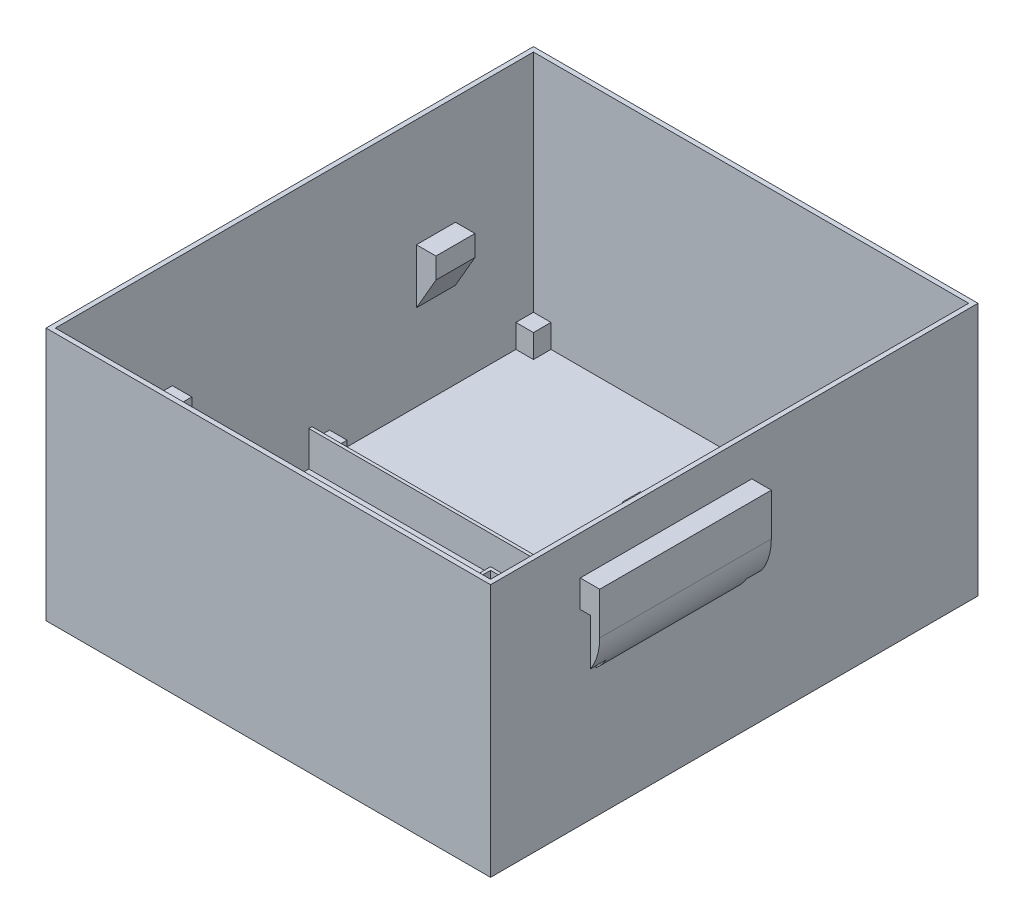
SolidWorks part; units mm, degrees
ref_plane "Front Plane" through (0, 0, 0) normal (0, 0, 1) x (1, 0, 0)
ref_plane "Top Plane" through (0, 0, 0) normal (0, 1, 0) x (1, 0, 0)
ref_plane "Right Plane" through (0, 0, 0) normal (1, 0, 0) x (0, 0, -1)
sketch "Sketch1" plane through (0, 0, 0) normal (0, 1, 0) x (1, 0, 0)
  line L1 (-57, 62.5) -> (57, 62.5)
  line L2 (-57, 62.5) -> (-57, -62.5)
  line L3 (-57, -62.5) -> (57, -62.5)
  line L4 (57, 62.5) -> (57, -62.5)
  line L5 (-57, 62.5) -> (57, -62.5) construction
  line L6 (-57, -62.5) -> (57, 62.5) construction
  point P0 (0, 0)
  dimension "D1" = 125
  dimension "D2" = 114
extrude "Boss-Extrude1" add sketch "Sketch1" along normal blind 65
sketch "Sketch2" plane through (0, 65, 0) normal (0, 1, 0) x (1, 0, 0)
  line L0 (57, -62.5) -> (57, 62.5) construction
  line L1 (-55.8, 61.3) -> (55.8, 61.3)
  line L2 (-55.8, 61.3) -> (-55.8, -61.3)
  line L3 (-55.8, -61.3) -> (55.8, -61.3)
  line L4 (55.8, 61.3) -> (55.8, -61.3)
  line L5 (-55.8, 61.3) -> (55.8, -61.3) construction
  line L6 (-55.8, -61.3) -> (55.8, 61.3) construction
  line L7 (-57, -62.5) -> (57, -62.5) construction
  point P0 (0, 0)
  dimension "D1" = 1.2
  dimension "D2" = 1.2
extrude "Cut-Extrude1" cut sketch "Sketch2" against normal blind 63.8
sketch "Sketch3" plane through (57, 0, 0) normal (1, 0, 0) x (0, 0, -1)
  line L1 (-39.5, 55) -> (4.5, 55)
  line L2 (-39.5, 55) -> (-39.5, 33)
  line L3 (-39.5, 33) -> (4.5, 33)
  line L4 (4.5, 55) -> (4.5, 33)
  line L5 (-62.5, 65) -> (-62.5, 0) construction
  line L6 (-62.5, 0) -> (62.5, 0) construction
  dimension "D1" = 22
  dimension "D2" = 44
  dimension "D3" = 23
  dimension "D4" = 33
extrude "Boss-Extrude2" add sketch "Sketch3" along normal blind 5
sketch "Sketch4" plane through (0, 0, 39.5) normal (0, 0, 1) x (1, 0, 0)
  line L1 (57, 33) -> (59.65, 33)
  line L2 (57, 33) -> (57, 48)
  line L3 (57, 48) -> (59.65, 48)
  line L4 (59.65, 33) -> (59.65, 48)
  dimension "D1" = 15
  dimension "D2" = 2.65
extrude "Cut-Extrude2" cut sketch "Sketch4" against normal blind 4
sketch "Sketch6" plane through (0, 0, -4.5) normal (0, 0, -1) x (-1, 0, 0)
  line L1 (-57, 33) -> (-59.65, 33)
  line L2 (-57, 33) -> (-57, 48)
  line L3 (-57, 48) -> (-59.65, 48)
  line L4 (-59.65, 33) -> (-59.65, 48)
  dimension "D1" = 2.65
  dimension "D2" = 15
extrude "Cut-Extrude3" cut sketch "Sketch6" against normal blind 4
mirror "Mirror5" about plane through (0, 0, 0) normal (1, 0, 0) of "Boss-Extrude2"
mirror "Mirror6" about plane through (0, 0, 0) normal (1, 0, 0) of "Cut-Extrude2"
mirror "Mirror7" about plane through (0, 0, 0) normal (1, 0, 0) of "Cut-Extrude3"
fillet "Fillet1" radius 15 1 edges at (62, 33, 17.5)
fillet "Fillet2" radius 15 1 edges at (-62, 33, 17.5)
sketch "Sketch7" plane through (0, 0, 61.3) normal (0, 0, -1) x (-1, 0, 0)
  line L1 (-50.8, 31.2) -> (-45.8, 31.2)
  line L2 (-50.8, 31.2) -> (-50.8, 1.2)
  line L3 (-50.8, 1.2) -> (-45.8, 1.2)
  line L4 (-45.8, 31.2) -> (-45.8, 1.2)
  line L5 (55.8, 1.2) -> (-55.8, 1.2) construction
  line L6 (-55.8, 1.2) -> (-55.8, 65) construction
  line L7 (-0.8, 31.2) -> (6.7, 31.2)
  line L8 (-0.8, 31.2) -> (-0.8, 1.2)
  line L9 (-0.8, 1.2) -> (6.7, 1.2)
  line L10 (6.7, 31.2) -> (6.7, 1.2)
  line L12 (46.7, 31.2) -> (51.7, 31.2)
  line L13 (46.7, 31.2) -> (46.7, 1.2)
  line L14 (46.7, 1.2) -> (51.7, 1.2)
  line L15 (51.7, 31.2) -> (51.7, 1.2)
  dimension "D1" = 7.5
  dimension "D2" = 50
  dimension "D3" = 5
  dimension "D4" = 5
  dimension "D5" = 5
  dimension "D6" = 45
  dimension "D7" = 30
  dimension "D8" = 30
  dimension "D9" = 30
extrude "Boss-Extrude3" [suppressed] add sketch "Sketch7" along normal blind 6
sketch "Sketch8" [suppressed] plane through (0, 60.8, 0) normal (0, 1, 0) x (1, 0, 0)
  line L1 (46.2, -59.7) -> (48.7, -59.7)
  line L2 (46.2, -59.7) -> (46.2, -57.7)
  line L3 (46.2, -57.7) -> (48.7, -57.7)
  line L4 (48.7, -59.7) -> (48.7, -57.7)
  line L5 (1.2, -59.7) -> (-1.3, -59.7)
  line L6 (1.2, -59.7) -> (1.2, -57.7)
  line L7 (1.2, -57.7) -> (-1.3, -57.7)
  line L8 (-1.3, -59.7) -> (-1.3, -57.7)
  line L9 (-6.3, -59.7) -> (-3.8, -59.7)
  line L10 (-6.3, -59.7) -> (-6.3, -57.7)
  line L11 (-6.3, -57.7) -> (-3.8, -57.7)
  line L12 (-3.8, -59.7) -> (-3.8, -57.7)
  line L13 (-46.3, -59.7) -> (-48.8, -59.7)
  line L14 (-46.3, -59.7) -> (-46.3, -57.7)
  line L15 (-46.3, -57.7) -> (-48.8, -57.7)
  line L16 (-48.8, -59.7) -> (-48.8, -57.7)
  line L17 (46.2, -61.7) -> (51.2, -61.7) construction
  line L19 (-6.3, -61.7) -> (1.2, -61.7) construction
  line L23 (-51.3, -61.7) -> (-46.3, -61.7) construction
  line L24 (46.2, -55.7) -> (46.2, -61.7) construction
  line L25 (1.2, -55.7) -> (1.2, -61.7) construction
  line L26 (-6.3, -55.7) -> (-6.3, -61.7) construction
  line L27 (-46.3, -55.7) -> (-46.3, -61.7) construction
  dimension "D1" = 2.5
  dimension "D2" = 2
  dimension "D3" = 2
  dimension "D4" = 2.5
  dimension "D5" = 2.5
  dimension "D6" = 2
  dimension "D7" = 2
  dimension "D8" = 2.5
  dimension "D9" = 2
  dimension "D10" = 2
  dimension "D11" = 2
  dimension "D12" = 2
extrude "Cut-Extrude4" [suppressed] cut sketch "Sketch8" against normal up to next
sketch "Sketch9" plane through (0, 1.2, 0) normal (0, 1, 0) x (1, 0, 0)
  line L0 (-55.8, -61.3) -> (55.8, -61.3) construction
  line L2 (-55.8, 61.3) -> (55.8, 61.3)
  line L3 (-55.8, 61.3) -> (-55.8, 3.7)
  line L4 (-55.8, 3.7) -> (55.8, 3.7)
  line L5 (-51.8, -8.7) -> (-3.2, -8.7)
  line L6 (-51.8, -8.7) -> (-51.8, -57.3)
  line L7 (-51.8, -57.3) -> (-3.2, -57.3)
  line L8 (-3.2, -8.7) -> (-3.2, -57.3)
  line L9 (-1.8, -3.7) -> (51.8, -3.7)
  line L10 (-1.8, -3.7) -> (-1.8, -57.3)
  line L11 (-1.8, -57.3) -> (51.8, -57.3)
  line L12 (51.8, -3.7) -> (51.8, -57.3)
  line L13 (-55.8, 61.3) -> (-55.8, -61.3) construction
  line L14 (55.8, -61.3) -> (55.8, 61.3) construction
  line L15 (55.8, 61.3) -> (55.8, 3.7)
  dimension "D2" = 57.6
  dimension "D3" = 48.6
  dimension "D4" = 48.6
  dimension "D5" = 53.6
  dimension "D6" = 53.6
  dimension "D7" = 4
  dimension "D8" = 4
  dimension "D9" = 4
  dimension "D10" = 4
extrude "Boss-Extrude4" add sketch "Sketch9" along normal blind 9
sketch "Sketch10" plane through (0, 10.2, 0) normal (0, 1, 0) x (1, 0, 0)
  line L0 (-55.8, 61.3) -> (-55.8, 3.7) construction
  line L1 (55.8, -61.3) -> (55.8, 3.7) construction
  line L2 (-3.2, -8.7) -> (-51.8, -8.7) construction
  line L5 (-55.8, 61.3) -> (55.8, 61.3)
  line L6 (-55.8, 61.3) -> (-55.8, 4.5)
  line L7 (-55.8, 4.5) -> (55.8, 4.5)
  line L8 (55.8, 61.3) -> (55.8, 4.5)
  line L9 (55.8, 61.3) -> (-55.8, 61.3) construction
  line L10 (-51, -9.5) -> (-4, -9.5)
  line L11 (-51, -9.5) -> (-51, -56.5)
  line L12 (-51, -56.5) -> (-4, -56.5)
  line L13 (-4, -9.5) -> (-4, -56.5)
  line L14 (-1, -4.5) -> (51, -4.5)
  line L15 (-1, -4.5) -> (-1, -56.5)
  line L16 (-1, -56.5) -> (51, -56.5)
  line L17 (51, -4.5) -> (51, -56.5)
  line L18 (-51.8, -8.7) -> (-51.8, -57.3) construction
  line L19 (-51.8, -57.3) -> (-3.2, -57.3) construction
  line L20 (-3.2, -57.3) -> (-3.2, -8.7) construction
  line L21 (-1.8, -57.3) -> (51.8, -57.3) construction
  line L22 (51.8, -57.3) -> (51.8, -3.7) construction
  line L23 (51.8, -3.7) -> (-1.8, -3.7) construction
  line L24 (-1.8, -3.7) -> (-1.8, -57.3) construction
  line L28 (-55.8, 3.7) -> (55.8, 3.7) construction
  dimension "D1" = 0.8
  dimension "D2" = 0.8
  dimension "D3" = 0.8
  dimension "D4" = 0.8
  dimension "D5" = 0.8
  dimension "D6" = 0.8
  dimension "D7" = 0.8
  dimension "D8" = 0.8
  dimension "D9" = 0.8
extrude "Cut-Extrude5" cut sketch "Sketch10" against normal blind 9
sketch "Sketch11" plane through (0, 1.2, 0) normal (0, 1, 0) x (1, 0, 0)
  line L0 (51, -4.5) -> (-1, -4.5) construction
  line L1 (-55.8, 61.3) -> (-51.3, 61.3)
  line L2 (-55.8, 61.3) -> (-55.8, 56.8)
  line L3 (-55.8, 56.8) -> (-51.3, 56.8)
  line L4 (-51.3, 61.3) -> (-51.3, 56.8)
  line L5 (-55.8, 4.5) -> (-51.3, 4.5)
  line L6 (-55.8, 4.5) -> (-55.8, 9)
  line L7 (-55.8, 9) -> (-51.3, 9)
  line L8 (-51.3, 4.5) -> (-51.3, 9)
  line L9 (55.8, 61.3) -> (-55.8, 61.3) construction
  line L10 (55.8, 4.5) -> (51.3, 4.5)
  line L11 (55.8, 4.5) -> (55.8, 61.3)
  line L12 (55.8, 61.3) -> (51.3, 61.3)
  line L13 (51.3, 4.5) -> (51.3, 61.3)
  line L17 (-51, -9.5) -> (-46.5, -9.5)
  line L18 (-51, -9.5) -> (-51, -14)
  line L19 (-51, -14) -> (-46.5, -14)
  line L20 (-46.5, -9.5) -> (-46.5, -14)
  line L21 (-1, -4.5) -> (3.5, -4.5)
  line L22 (-1, -4.5) -> (-1, -9)
  line L23 (-1, -9) -> (3.5, -9)
  line L24 (3.5, -4.5) -> (3.5, -9)
  line L25 (-4, -9.5) -> (-8.5, -9.5)
  line L26 (-4, -9.5) -> (-4, -14)
  line L27 (-4, -14) -> (-8.5, -14)
  line L28 (-8.5, -9.5) -> (-8.5, -14)
  line L29 (51, -4.5) -> (46.5, -4.5)
  line L30 (51, -4.5) -> (51, -9)
  line L31 (51, -9) -> (46.5, -9)
  line L32 (46.5, -4.5) -> (46.5, -9)
  line L33 (51, -56.5) -> (51, -4.5) construction
  line L34 (-51, -9.5) -> (-51, -56.5) construction
  line L35 (-51, -56.5) -> (-46.5, -56.5)
  line L36 (-51, -56.5) -> (-51, -52)
  line L37 (-51, -52) -> (-46.5, -52)
  line L38 (-46.5, -56.5) -> (-46.5, -52)
  line L39 (-51, -56.5) -> (-4, -56.5) construction
  line L40 (0, 7.1856) -> (0, 46.953) construction
  line L41 (-1, -56.5) -> (3.5, -56.5)
  line L42 (-1, -56.5) -> (-1, -52)
  line L43 (-1, -52) -> (3.5, -52)
  line L44 (3.5, -56.5) -> (3.5, -52)
  line L45 (-4, -56.5) -> (-8.5, -56.5)
  line L46 (-4, -56.5) -> (-4, -52)
  line L47 (-4, -52) -> (-8.5, -52)
  line L48 (-8.5, -56.5) -> (-8.5, -52)
  line L49 (51, -56.5) -> (46.5, -56.5)
  line L50 (51, -56.5) -> (51, -52)
  line L51 (51, -52) -> (46.5, -52)
  line L52 (46.5, -56.5) -> (46.5, -52)
  line L53 (-2.25, 35.15) -> (2.25, 35.15)
  line L54 (-2.25, 35.15) -> (-2.25, 30.65)
  line L55 (-2.25, 30.65) -> (2.25, 30.65)
  line L56 (2.25, 35.15) -> (2.25, 30.65)
  line L57 (-2.25, 35.15) -> (2.25, 30.65) construction
  line L58 (-2.25, 30.65) -> (2.25, 35.15) construction
  line L59 (55.8, 32.9) -> (-23.3094, 32.9) construction
  line L60 (55.8, 4.5) -> (55.8, 61.3) construction
  point P66 (0, 32.9)
  dimension "D1" = 4.5
  dimension "D2" = 4.5
  dimension "D3" = 4.5
  dimension "D4" = 4.5
  dimension "D5" = 4.5
  dimension "D9" = 4.5
  dimension "D10" = 4.5
  dimension "D11" = 4.5
  dimension "D12" = 4.5
  dimension "D13" = 4.5
  dimension "D14" = 4.5
  dimension "D15" = 4.5
  dimension "D16" = 4.5
  dimension "D17" = 4.5
  dimension "D18" = 4.5
  dimension "D19" = 4.5
  dimension "D20" = 4.5
  dimension "D21" = 4.5
  dimension "D22" = 4.5
  dimension "D23" = 4.5
  dimension "D24" = 4.5
  dimension "D25" = 4.5
  dimension "D26" = 4.5
extrude "Boss-Extrude5" add sketch "Sketch11" along normal blind 6
sketch "Sketch12" plane through (55.8, 0, 0) normal (-1, 0, 0) x (0, 0, 1)
  line L1 (-41.3, 37.2) -> (-31.3, 37.2)
  line L2 (-41.3, 37.2) -> (-41.3, 32.2)
  line L3 (-41.3, 32.2) -> (-31.3, 32.2)
  line L4 (-31.3, 37.2) -> (-31.3, 32.2)
  line L5 (31.3, 37.2) -> (41.3, 37.2)
  line L6 (31.3, 37.2) -> (31.3, 32.2)
  line L7 (31.3, 32.2) -> (41.3, 32.2)
  line L8 (41.3, 37.2) -> (41.3, 32.2)
  line L11 (-61.3, 7.2) -> (-61.3, 65) construction
  line L12 (61.3, 1.2) -> (61.3, 65) construction
  line L13 (56.5, 7.2) -> (52, 7.2) construction
  line L15 (-4.5, 7.2) -> (-61.3, 7.2) construction
  dimension "D1" = 10
  dimension "D2" = 10
  dimension "D3" = 5
  dimension "D4" = 5
  dimension "D5" = 30
  dimension "D6" = 30
  dimension "D7" = 20
  dimension "D8" = 20
extrude "Boss-Extrude6" add sketch "Sketch12" along normal blind 5
chamfer "Chamfer1" distance 9 angle 30 2 edges at (55.8, 32.2, 36.3) (55.8, 32.2, -36.3) first distance on face at (55.8, 34.7, -36.3)
mirror "Mirror8" about plane through (0, 0, 0) normal (1, 0, 0) of "Chamfer1", "Boss-Extrude6"
